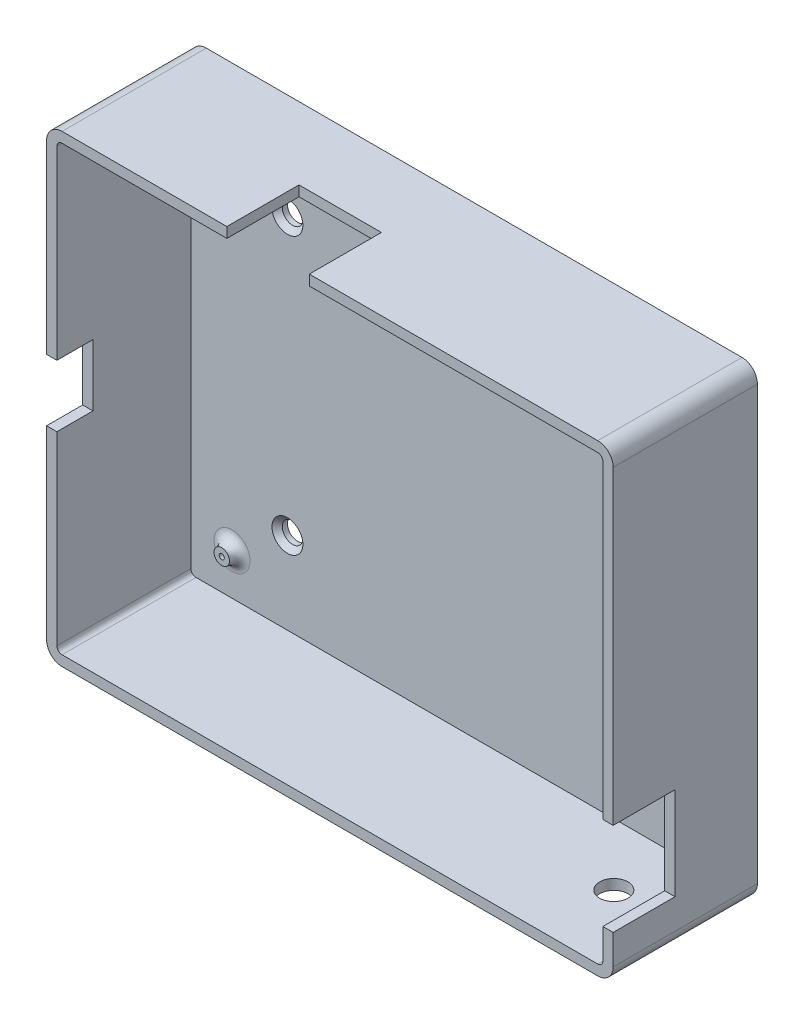
SolidWorks part; units mm, degrees
ref_plane "Front Plane" through (0, 0, 0) normal (0, 0, 1) x (1, 0, 0)
ref_plane "Top Plane" through (0, 0, 0) normal (0, 1, 0) x (1, 0, 0)
ref_plane "Right Plane" through (0, 0, 0) normal (1, 0, 0) x (0, 0, -1)
sketch "Sketch2" plane through (0, 0, 0) normal (0, 0, 1) x (1, 0, 0)
  line L1 (-52, -45) -> (52, -45)
  line L2 (-55, -42) -> (-55, 42)
  line L3 (-52, 45) -> (52, 45)
  line L4 (55, -42) -> (55, 42)
  line L5 (-55, -45) -> (55, 45) construction
  line L6 (-55, 45) -> (55, -45) construction
  arc A0 (52, -45) -> (55, -42) centre (52, -42) ccw
  arc A1 (-52, -45) -> (-55, -42) centre (-52, -42) cw
  arc A2 (-55, 42) -> (-52, 45) centre (-52, 42) cw
  arc A3 (52, 45) -> (55, 42) centre (52, 42) cw
  point P0 (0, 0)
  dimension "D3" = 3
  dimension "D1" = 90
  dimension "D2" = 110
extrude "Boss-Extrude1" add sketch "Sketch2" along normal blind 2
sketch "Sketch3" plane through (0, 0, 2) normal (0, 0, 1) x (1, 0, 0)
  line L0 (52, 43) -> (-52, 43)
  line L1 (-53, 42) -> (-53, -42)
  line L2 (-52, -43) -> (52, -43)
  line L3 (53, -42) -> (53, 42)
  line L4 (55, -42) -> (55, 42)
  line L5 (52, 45) -> (-52, 45)
  line L6 (-55, 42) -> (-55, -42)
  line L7 (-52, -45) -> (52, -45)
  line L8 (55, -42) -> (55, 42)
  line L9 (52, 45) -> (-52, 45)
  line L10 (-55, 42) -> (-55, -42)
  line L11 (-52, -45) -> (52, -45)
  arc A0 (-52, 43) -> (-53, 42) centre (-52, 42) ccw
  arc A1 (-53, -42) -> (-52, -43) centre (-52, -42) ccw
  arc A2 (52, -43) -> (53, -42) centre (52, -42) ccw
  arc A3 (53, 42) -> (52, 43) centre (52, 42) ccw
  arc A4 (52, -45) -> (55, -42) centre (52, -42) ccw
  arc A5 (55, 42) -> (52, 45) centre (52, 42) ccw
  arc A6 (-52, 45) -> (-55, 42) centre (-52, 42) ccw
  arc A7 (-55, -42) -> (-52, -45) centre (-52, -42) ccw
  arc A8 (52, -45) -> (55, -42) centre (52, -42) ccw
  arc A9 (55, 42) -> (52, 45) centre (52, 42) ccw
  arc A10 (-52, 45) -> (-55, 42) centre (-52, 42) ccw
  arc A11 (-55, -42) -> (-52, -45) centre (-52, -42) ccw
  dimension "D1" = 0
  dimension "D2" = 2
extrude "Boss-Extrude2" add sketch "Sketch3" along normal blind 26
sketch "Sketch5" plane through (0, 0, 0) normal (0, 0, -1) x (-1, 0, 0)
  line L1 (-45, -35) -> (45, -35) construction
  line L2 (-45, -35) -> (-45, 35) construction
  line L3 (-45, 35) -> (45, 35) construction
  line L4 (45, -35) -> (45, 35) construction
  line L5 (-45, -35) -> (45, 35) construction
  line L6 (-45, 35) -> (45, -35) construction
  circle A0 centre (45, 35) radius 0.5
  circle A1 centre (-45, 35) radius 0.5
  circle A2 centre (-45, -35) radius 0.5
  circle A3 centre (45, -35) radius 0.5
  circle A4 centre (45, 35) radius 1.5
  circle A5 centre (-45, 35) radius 1.5
  circle A6 centre (-45, -35) radius 1.5
  circle A7 centre (45, -35) radius 1.5
  point P0 (0, 0)
  dimension "D1" = 1
  dimension "D2" = 70
  dimension "D3" = 90
extrude "Boss-Extrude4" add sketch "Sketch5" against normal blind 4
fillet "Fillet2" radius 2 4 edges at (-43.5, -35, 2) (46.5, -35, 2) (46.5, 35, 2) (-43.5, 35, 2)
sketch "Sketch8" plane through (0, 0, 2) normal (0, 0, 1) x (1, 0, 0)
  line L0 (45, -35) -> (45, 35) construction
  line L1 (45, 35) -> (45, 43) construction
  line L2 (52, 43) -> (-52, 43) construction
sketch "Sketch9" plane through (0, 43, 0) normal (0, -1, 0) x (-1, 0, 0)
  line L0 (-45, -2) -> (-45, -28) construction
  line L1 (-52, -28) -> (52, -28) construction
  line L2 (12, -2) -> (12, -28) construction
  line L3 (-52, -2) -> (52, -2) construction
  line L5 (20, -14) -> (4, -14)
  line L6 (20, -14) -> (20, -28)
  line L7 (20, -28) -> (4, -28)
  line L8 (4, -14) -> (4, -28)
  line L9 (20, -14) -> (4, -28) construction
  line L10 (20, -28) -> (4, -14) construction
  point P9 (12, -21)
  dimension "D1" = 57
  dimension "D2" = 12
  dimension "D3" = 16
extrude "Cut-Extrude3" cut sketch "Sketch9" against normal blind 2.5
sketch "Sketch11" plane through (0, -45, 0) normal (0, -1, 0) x (-1, 0, 0)
  line L0 (-52, -14) -> (52, -14) construction
  line L1 (-52, -28) -> (-52, 0) construction
  line L2 (52, -28) -> (52, 0) construction
  circle A0 centre (-41.1265, -14) radius 2.75
extrude "Cut-Extrude5" cut sketch "Sketch11" against normal blind 2.5
sketch "Sketch12" plane through (-55, 0, 0) normal (-1, 0, 0) x (0, 0, 1)
  line L0 (28, 42) -> (28, -42) construction
  line L1 (28, 6) -> (21, 6)
  line L2 (28, 6) -> (28, -6)
  line L3 (28, -6) -> (21, -6)
  line L4 (21, 6) -> (21, -6)
  line L5 (0, 0) -> (28, 0) construction
  line L6 (0, 42) -> (0, -42) construction
  line L7 (28, 6) -> (21, -6) construction
  line L8 (28, -6) -> (21, 6) construction
  point P10 (24.5, 0)
  dimension "D1" = 7
  dimension "D2" = 12
extrude "Cut-Extrude6" cut sketch "Sketch12" against normal up to next
sketch "Sketch13" plane through (55, 0, 0) normal (1, 0, 0) x (0, 0, -1)
  line L0 (-28, -42) -> (-28, 42) construction
  line L1 (-28, -36.1902) -> (-16, -36.1902)
  line L2 (-28, -36.1902) -> (-28, -18.1902)
  line L3 (-28, -18.1902) -> (-16, -18.1902)
  line L4 (-16, -36.1902) -> (-16, -18.1902)
  dimension "D1" = 12
  dimension "D2" = 18
extrude "Cut-Extrude7" cut sketch "Sketch13" against normal blind 10
sketch "Sketch14" plane through (0, 0, 2) normal (0, 0, 1) x (1, 0, 0)
  line L0 (-45, -35.5) -> (45, 35) construction
  line L1 (0, -0.25) -> (-10.4169, 13.0482) construction
  line L2 (0, -0.25) -> (-47.0216, -0.25) construction
  circle A0 centre (-45, -35) radius 0.5 construction
  circle A1 centre (-34.2439, -27.0744) radius 2
  circle A2 centre (34.2439, 26.5744) radius 2
  circle A3 centre (34.2439, -27.0744) radius 2
  circle A4 centre (-34.2439, 26.5744) radius 2
  dimension "D1" = 4
extrude "Cut-Extrude8" cut sketch "Sketch14" against normal blind 10
chamfer "Chamfer1" distance 1 4 edges at (32.2439, 26.5744, 2) (-32.2439, -27.0744, 2) (36.2439, -27.0744, 2) (-36.2439, 26.5744, 2)
